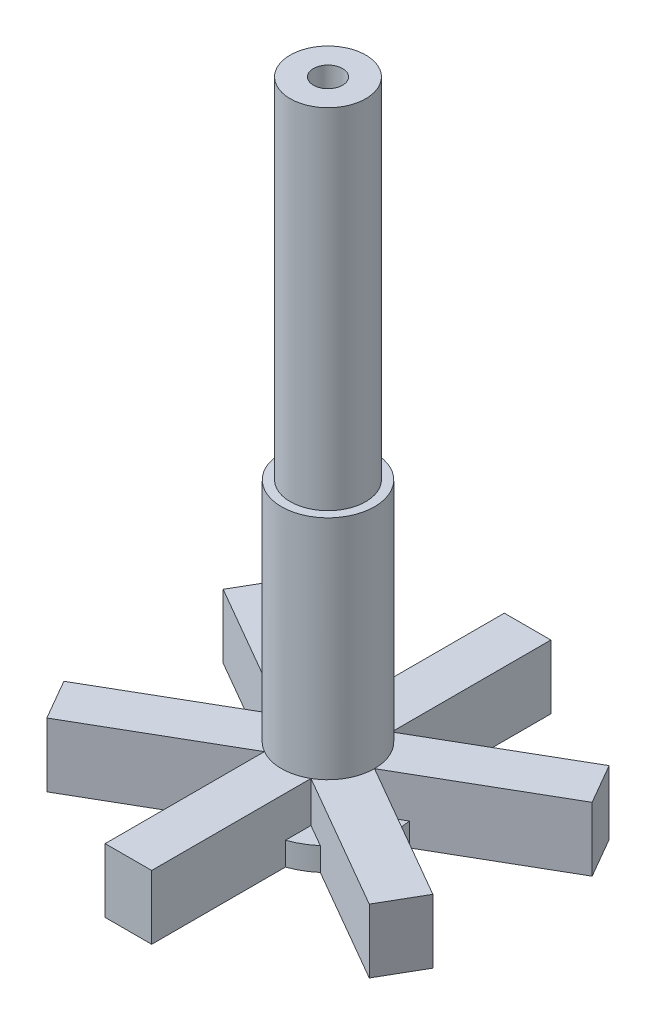
SolidWorks part; units mm, degrees
ref_plane "Front Plane" through (0, 0, 0) normal (0, 0, 1) x (1, 0, 0)
ref_plane "Top Plane" through (0, 0, 0) normal (0, 1, 0) x (1, 0, 0)
ref_plane "Right Plane" through (0, 0, 0) normal (1, 0, 0) x (0, 0, -1)
sketch "Sketch1" plane through (0, 0, 0) normal (0, 1, 0) x (1, 0, 0)
  line L48 (-2, -5.6569) -> (2, -5.6569)
  line L55 (2, -5.6569) -> (2, -17.1569)
  line L62 (2, -17.1569) -> (-2, -17.1569)
  line L69 (-2, -17.1569) -> (-2, -5.6569)
  line L70 (-15.8583, -6.8464) -> (-5.899, -1.0964)
  line L71 (-5.899, -1.0964) -> (-3.899, -4.5605)
  line L72 (-3.899, -4.5605) -> (-13.8583, -10.3105)
  line L73 (-13.8583, -10.3105) -> (-15.8583, -6.8464)
  line L74 (-13.8583, 10.3105) -> (-3.899, 4.5605)
  line L75 (-3.899, 4.5605) -> (-5.899, 1.0964)
  line L76 (-5.899, 1.0964) -> (-15.8583, 6.8464)
  line L77 (-15.8583, 6.8464) -> (-13.8583, 10.3105)
  line L78 (2, 17.1569) -> (2, 5.6569)
  line L79 (2, 5.6569) -> (-2, 5.6569)
  line L80 (-2, 5.6569) -> (-2, 17.1569)
  line L81 (-2, 17.1569) -> (2, 17.1569)
  line L82 (15.8583, 6.8464) -> (5.899, 1.0964)
  line L83 (5.899, 1.0964) -> (3.899, 4.5605)
  line L84 (3.899, 4.5605) -> (13.8583, 10.3105)
  line L85 (13.8583, 10.3105) -> (15.8583, 6.8464)
  line L86 (13.8583, -10.3105) -> (3.899, -4.5605)
  line L87 (3.899, -4.5605) -> (5.899, -1.0964)
  line L88 (5.899, -1.0964) -> (15.8583, -6.8464)
  line L89 (15.8583, -6.8464) -> (13.8583, -10.3105)
  line L90 (-2, 5.6569) -> (-2, 3.4641)
  line L91 (2, 5.6569) -> (2, 3.4641)
  line L92 (3.899, 4.5605) -> (2, 3.4641)
  line L93 (5.899, 1.0964) -> (4, 0)
  line L94 (5.899, -1.0964) -> (4, 0)
  line L95 (3.899, -4.5605) -> (2, -3.4641)
  line L96 (2, -5.6569) -> (2, -3.4641)
  line L97 (-2, -5.6569) -> (-2, -3.4641)
  line L98 (-3.899, -4.5605) -> (-2, -3.4641)
  line L99 (-5.899, -1.0964) -> (-4, 0)
  line L100 (-5.899, 1.0964) -> (-4, 0)
  line L101 (-3.899, 4.5605) -> (-2, 3.4641)
  circle A2 centre (0, 0) radius 4
  arc A3 (2, -5.6569) -> (3.899, -4.5605) centre (0, 0) ccw
  arc A4 (-3.899, -4.5605) -> (-2, -5.6569) centre (0, 0) ccw
  arc A5 (-5.899, 1.0964) -> (-5.899, -1.0964) centre (0, 0) ccw
  arc A6 (-2, 5.6569) -> (-3.899, 4.5605) centre (0, 0) ccw
  arc A7 (3.899, 4.5605) -> (2, 5.6569) centre (0, 0) ccw
  arc A8 (5.899, -1.0964) -> (5.899, 1.0964) centre (0, 0) ccw
  point P9 (0, -5.6569)
  point P31 (0, 0)
  point P32 (0, 0)
  point P33 (0, 0)
  point P46 (0.0289, 0.0554)
  dimension "D1" = 8
  dimension "D2" = 6
  dimension "D3" = 2
  dimension "D4" = 4
  dimension "D5" = 11.5
  dimension "D6" = 6
extrude "Boss-Extrude1" add sketch "Sketch1" along normal blind 25 contours A2
extrude "Boss-Extrude3" add sketch "Sketch1<4>" along normal blind 2 contours L90 A6 L101 | A2 L101 L75 L100 | L100 A5 L99 | A2 L99 L71 L98 | L98 A4 L97 | A2 L97 L48 L96 | L96 A3 L95 | A2 L95 L87 L94 | L94 A8 L93 | A2 L93 L83 L92 | L92 A7 L91 | A2 L91 L79 L90 region at (0, 0, 4.7348) region at (-2.6553, 0, 4.5992) region at (2.6553, 0, 4.5992) region at (-4.1005, 0, 2.3674) region at (4.1005, 0, 2.3674) region at (-5.3107, 0, 0) region at (-4.1005, 0, -2.3674) region at (4.1005, 0, -2.3674) region at (5.3107, 0, 0) region at (-2.6553, 0, -4.5992) region at (0, 0, -4.7348) region at (2.6553, 0, -4.5992)
sketch "Sketch1<4>" plane through (0, 0, 0) normal (0, 1, 0) x (1, 0, 0) same geometry as "Sketch1"
extrude "Boss-Extrude2" add sketch "Sketch1<3>" along normal blind 5.5 contours L62 | A2 L99 L71 L98 | A2 L95 L87 L94 | A2 L93 L83 L92 | A2 L91 L79 L90 | A2 L101 L75 L100 | A2 L97 L48 L96 | L69 L48 L55 L62 | L70 L71 L72 L73 | L74 L75 L76 L77 | L78 L79 L80 L81 | L82 L83 L84 L85 | L86 L87 L88 L89 region at (0, 0, 4.7348) region at (-4.1005, 0, 2.3674) region at (4.1005, 0, 2.3674) region at (-4.1005, 0, -2.3674) region at (4.1005, 0, -2.3674) region at (0, 0, -4.7348)
sketch "Sketch1<3>" plane through (0, 0, 0) normal (0, 1, 0) x (1, 0, 0) same geometry as "Sketch1"
sketch "Sketch2" plane through (0, 25, 0) normal (0, 1, 0) x (1, 0, 0)
  circle A1 centre (0, 0) radius 3.25
  circle A3 centre (0, 0) radius 1.25
  dimension "D1" = 2
  dimension "D2" = 2.5
extrude "Boss-Extrude6" add sketch "Sketch2" along normal blind 30 contours A1
sketch "Sketch3" plane through (0, 55, 0) normal (0, 1, 0) x (1, 0, 0)
  circle A0 centre (0, 0) radius 1.25
  circle A2 centre (0, 0) radius 3.25 construction
  dimension "D1" = 2
extrude "Cut-Extrude1" cut sketch "Sketch3" against normal blind 10
